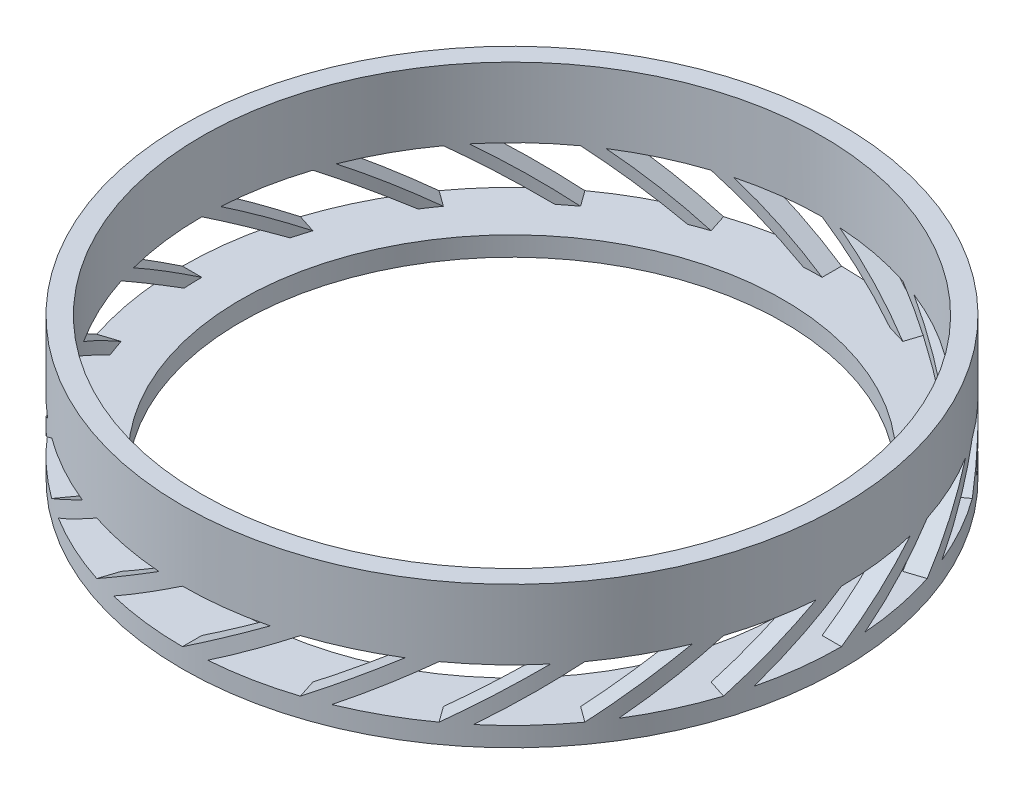
SolidWorks part; units mm, degrees
ref_plane "Front Plane" through (0, 0, 0) normal (0, 0, 1) x (1, 0, 0)
ref_plane "Top Plane" through (0, 0, 0) normal (0, 1, 0) x (1, 0, 0)
ref_plane "Right Plane" through (0, 0, 0) normal (1, 0, 0) x (0, 0, -1)
sketch "Sketch2" plane through (0, 0, 0) normal (0, 1, 0) x (1, 0, 0)
  circle A0 centre (0, 0) radius 26.9875
extrude "Boss-Extrude1" add sketch "Sketch2" along normal blind 11.5951
shell "Shell1" thickness 1.5875 removed face at (0, 11.5951, 26.9875)
ref_axis "Axis1" through (0, 11.5951, 0) along (0, -1, 0)
sketch "Sketch5" plane through (0, 1.5875, 0) normal (0, 1, 0) x (1, 0, 0)
  circle A0 centre (0, 0) radius 22.225
  dimension "D1" = 44.45
extrude "Cut-Extrude1" cut sketch "Sketch5" against normal through all both and the other way through all
sketch "Sketch6" plane through (0, 0, 0) normal (0, 0, 1) x (1, 0, 0)
  line L0 (0, 1.5875) -> (6.4136, 1.5875)
  line L1 (26.9875, 11.5951) -> (-26.9875, 11.5951) construction
  line L2 (0, 1.5875) -> (-6.4136, 5.8801)
  line L3 (0, 11.5951) -> (0, 8.356)
  line L8 (0, 0) -> (0, 1.5875)
  line L9 (0, 1.5875) -> (6.4136, 1.5875)
  line L13 (0, 1.5875) -> (0, 5.8801)
  line L14 (6.4136, 1.5875) -> (0, 5.8801)
  line L15 (-6.4136, 5.8801) -> (0, 5.8801)
extrude "Cut-Extrude2" cut sketch "Sketch6" against normal blind 38.1 contours L9 | L0 L2 L15 L14 region at (2.1379, 3.0184, 0)
pattern_circular "CirPattern3" count 20 over 360 about axis through (0, 11.5951, 0) along (0, -1, 0) of "Cut-Extrude2"
